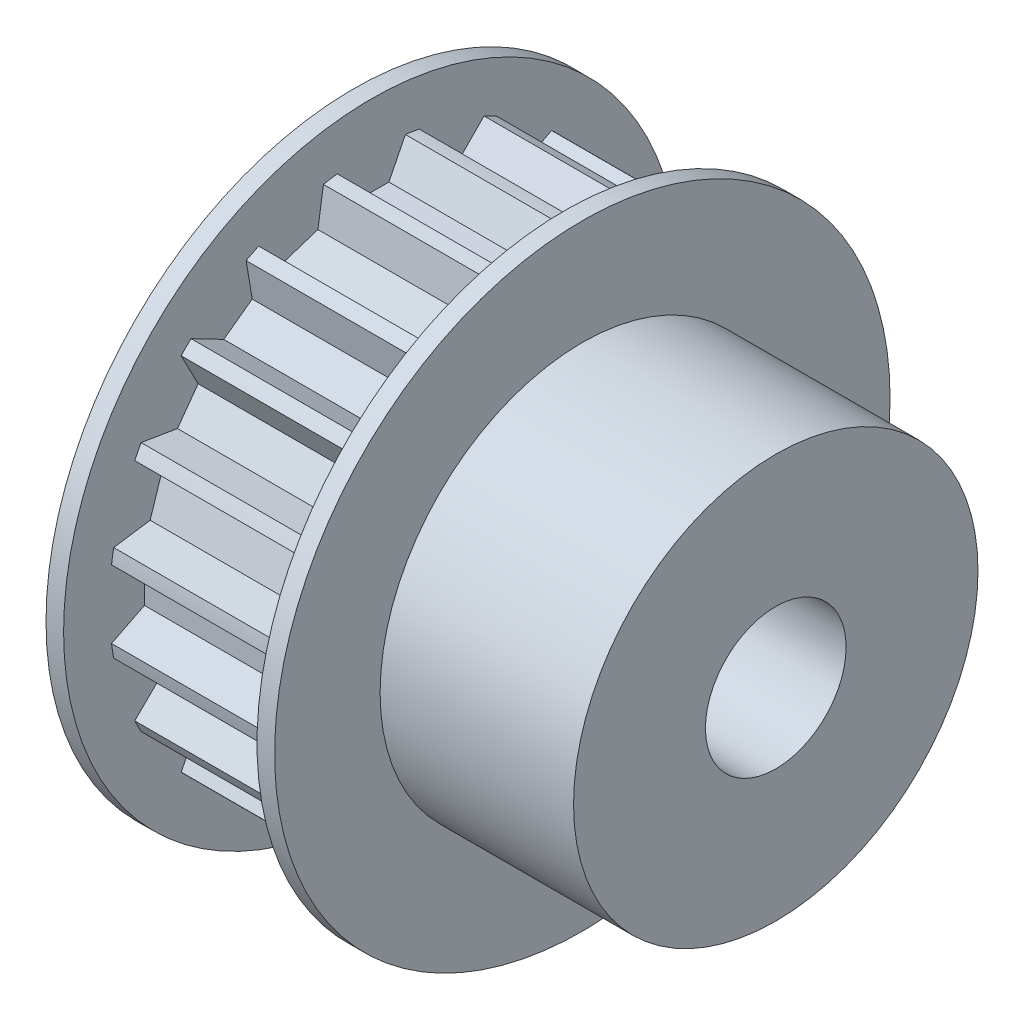
SolidWorks part; units mm, degrees
ref_plane "Front Plane" through (0, 0, 0) normal (0, 0, 1) x (1, 0, 0)
ref_plane "Top Plane" through (0, 0, 0) normal (0, 1, 0) x (1, 0, 0)
ref_plane "Right Plane" through (0, 0, 0) normal (1, 0, 0) x (0, 0, -1)
sketch "Sketch1" plane through (0, 0, 0) normal (1, 0, 0) x (0, 0, -1)
  circle A0 centre (0, 0) radius 14.9
  circle A1 centre (0, 0) radius 4
  dimension "D1" = 8
  dimension "D2" = 29.8
extrude "Boss-Extrude1" add sketch "Sketch1" along normal mid plane 11
sketch "Sketch2" plane through (5.5, 0, 0) normal (1, 0, 0) x (0, 0, -1)
  circle A1 centre (0, 0) radius 4
  circle A2 centre (0, 0) radius 11.5
  dimension "D1" = 8
  dimension "D2" = 23
extrude "Boss-Extrude2" add sketch "Sketch2" along normal blind 12
sketch "Sketch6" plane through (-5.5, 0, 0) normal (-1, 0, 0) x (0, 0, 1)
  line L0 (0, 0) -> (0, 14.9) construction
  line L1 (-1, 12.9) -> (1, 12.9)
  line L2 (1, 12.9) -> (2, 14.9)
  line L3 (2, 14.9) -> (-2, 14.9)
  line L4 (-2, 14.9) -> (-1, 12.9)
  circle A0 centre (0, 0) radius 14.9 construction
  dimension "D1" = 1
  dimension "D2" = 1
  dimension "D3" = 2
  dimension "D4" = 2
  dimension "D5" = 2
extrude "Cut-Extrude2" cut sketch "Sketch6" against normal up to surface (11 mm away) up to face at (5.5, 0, -11.5)
pattern_circular "CirPattern2" count 20 over 360 about axis through (-5.5, 0, 0) along (1, 0, 0) of "Cut-Extrude2"
sketch "Sketch7" plane through (-5.5, 0, 0) normal (-1, 0, 0) x (0, 0, 1)
  circle A0 centre (0, 0) radius 17.5
  circle A1 centre (0, 0) radius 4
  dimension "D1" = 8
  dimension "D2" = 35
extrude "Boss-Extrude3" add sketch "Sketch7" along normal blind 1
sketch "Sketch8" plane through (5.5, 0, 0) normal (1, 0, 0) x (0, 0, -1)
  circle A0 centre (0, 0) radius 17.5
  circle A1 centre (0, 0) radius 4
  dimension "D1" = 8
  dimension "D2" = 35
extrude "Boss-Extrude4" add sketch "Sketch8" along normal blind 1
